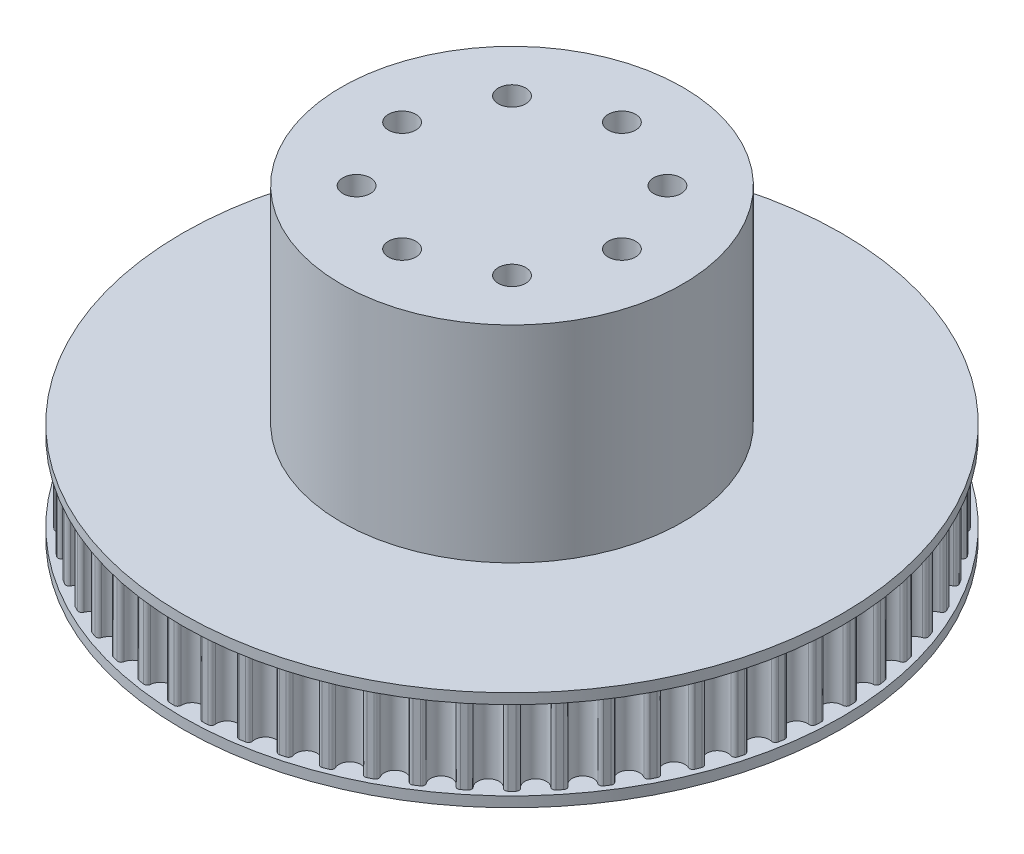
SolidWorks part; units mm, degrees
ref_plane "前视基准面" through (0, 0, 0) normal (0, 0, 1) x (1, 0, 0)
ref_plane "上视基准面" through (0, 0, 0) normal (0, 1, 0) x (1, 0, 0)
ref_plane "右视基准面" through (0, 0, 0) normal (1, 0, 0) x (0, 0, -1)
other "Configuration Table"
sketch "草图1" plane through (0, 0, 0) normal (0, 1, 0) x (1, 0, 0)
  circle A1 centre (0, 0) radius 47.175
  dimension "D2" = 94.35
extrude "凸台-拉伸1" add sketch "草图1" along normal blind 11.5
sketch "草图2" plane through (0, 11.5, 0) normal (0, 1, 0) x (1, 0, 0)
  line L0 (0, 0) -> (0, 47.745) construction
  line L1 (0, 47.745) -> (0, 47.175)
  line L2 (0, 47.175) -> (0, 45.015)
  line L3 (-1.625, 47.175) -> (1.625, 47.175)
  line L4 (-1.56, 46.575) -> (-1.6999, 47.7147)
  line L5 (1.56, 46.575) -> (1.6999, 47.7147)
  circle A0 centre (0, 0) radius 47.745 construction
  circle A1 centre (0, 46.575) radius 1.56
  point P11 (0, 47.175)
  point P17 (0, 46.575)
  circle M9 centre (0, 0) radius 47.175
  dimension "D1" = 95.49
  dimension "D4" = 3.12
  dimension "D2" = 0.57
  dimension "D3" = 2.16
  dimension "D5" = 3.25
  dimension "D6" = 7
  dimension "D7" = 7
  dimension "D8" = 1.56
extrude "切除-拉伸1" cut sketch "草图2" against normal through all contours A1 L2 M9 | A1 L2 M9 region at (0.6925, 11.5, -46.2189) region at (-0.6925, 11.5, -46.2189)
fillet "圆角1" radius 0.5 2 edges at (1.4491, 5.75, -47.1527) (-1.4491, 5.75, -47.1527)
pattern_circular "阵列(圆周)1" count 60 over 360 about axis through (0, 11.5, 0) along (0, 1, 0) of "圆角1", "切除-拉伸1"
sketch "草图5" plane through (0, 0, 0) normal (0, -1, 0) x (1, 0, 0)
  circle A0 centre (0, 0) radius 48
  dimension "D1" = 96
extrude "凸台-拉伸2" add sketch "草图5" along normal blind 1.5
sketch "草图6" plane through (0, -1.5, 0) normal (0, -1, 0) x (1, 0, 0)
  circle A0 centre (0, 0) radius 32.6
  dimension "D1" = 65.2
extrude "切除-拉伸4" cut sketch "草图6" against normal blind 8.7
sketch "草图7" plane through (0, -1.5, 0) normal (0, -1, 0) x (1, 0, 0)
  circle A0 centre (0, 0) radius 34.1
  dimension "D1" = 68.2
extrude "切除-拉伸5" cut sketch "草图7" against normal blind 1.7
sketch "草图8" plane through (0, 11.5, 0) normal (0, 1, 0) x (1, 0, 0)
  circle A0 centre (0, 0) radius 48
extrude "凸台-拉伸3" add sketch "草图8" along normal blind 1.5
sketch "草图9" plane through (0, 7.2, 0) normal (0, -1, 0) x (1, 0, 0)
  circle A0 centre (0, 0) radius 22.5
  dimension "D1" = 45
extrude "切除-拉伸7" cut sketch "草图9" against normal blind 2
sketch "草图10" plane through (0, 13, 0) normal (0, 1, 0) x (1, 0, 0)
  circle A0 centre (0, 0) radius 24.85
  circle A1 centre (0, 0) radius 19.85
  dimension "D1" = 49.7
  dimension "D2" = 5
extrude "凸台-拉伸4" add sketch "草图10" along normal blind 30
sketch "草图11" plane through (0, 43, 0) normal (0, 1, 0) x (1, 0, 0)
  circle A1 centre (0, 0) radius 24.85
  circle A2 centre (0, 0) radius 24.85
  dimension "D1" = 0
extrude "凸台-拉伸5" add sketch "草图11" against normal blind 3
sketch "草图12" plane through (0, 9.2, 0) normal (0, -1, 0) x (1, 0, 0)
  circle A0 centre (0, 0) radius 19.85
extrude "切除-拉伸8" cut sketch "草图12" against normal blind 12
sketch "草图13" plane through (0, 40, 0) normal (0, -1, 0) x (1, 0, 0)
  circle A1 centre (0, 0) radius 19.85
  circle A2 centre (0, 0) radius 19.85
  circle A3 centre (0, -16) radius 2
  dimension "D3" = 4
  dimension "D2" = 16
  dimension "D1" = 0
extrude "切除-拉伸9" cut sketch "草图13" against normal through all contours A3
pattern_circular "阵列(圆周)2" count 8 over 360 about axis through (0, 43, 0) along (0, -1, 0) of "切除-拉伸9"
